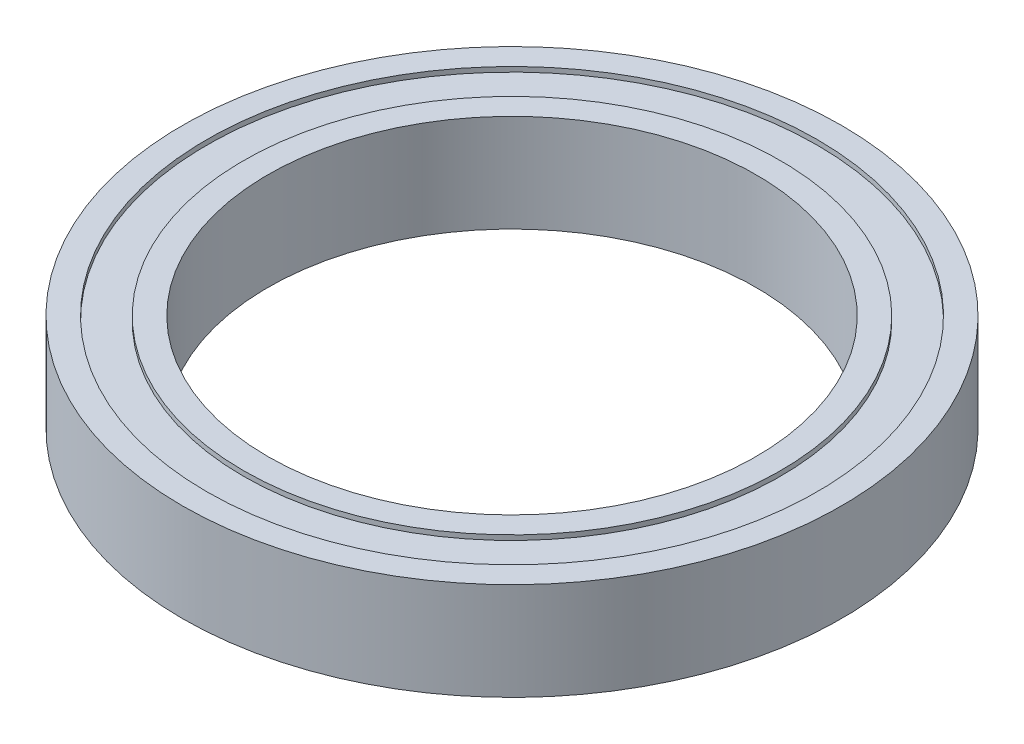
SolidWorks part; units mm, degrees
ref_plane "Front Plane" through (0, 0, 0) normal (0, 0, 1) x (1, 0, 0)
ref_plane "Top Plane" through (0, 0, 0) normal (0, 1, 0) x (1, 0, 0)
ref_plane "Right Plane" through (0, 0, 0) normal (1, 0, 0) x (0, 0, -1)
sketch "Sketch1" plane through (0, 0, 0) normal (0, 1, 0) x (1, 0, 0)
  circle A0 centre (0, 0) radius 10
  circle A1 centre (0, 0) radius 13.5
  dimension "D1" = 20
  dimension "D2" = 27
extrude "Boss-Extrude1" add sketch "Sketch1" along normal mid plane 4
sketch "Sketch2" plane through (0, 0, 0) normal (0, -1, 0) x (1, 0, 0)
  circle A2 centre (0, 0) radius 11
  circle A3 centre (0, 0) radius 11
  circle A5 centre (0, 0) radius 12.5
  circle A6 centre (0, 0) radius 12.5
  dimension "D1" = 1
  dimension "D2" = 1
extrude "Cut-Extrude1" cut sketch "Sketch2" against normal blind 0.2 from surface starting at face at (0, -2, 13.5)
extrude "Cut-Extrude2" cut sketch "Sketch2<2>" along normal blind 0.2 from surface starting at face at (0, 2, 13.5)
sketch "Sketch2<2>" plane through (0, 0, 0) normal (0, -1, 0) x (1, 0, 0) same geometry as "Sketch2"
